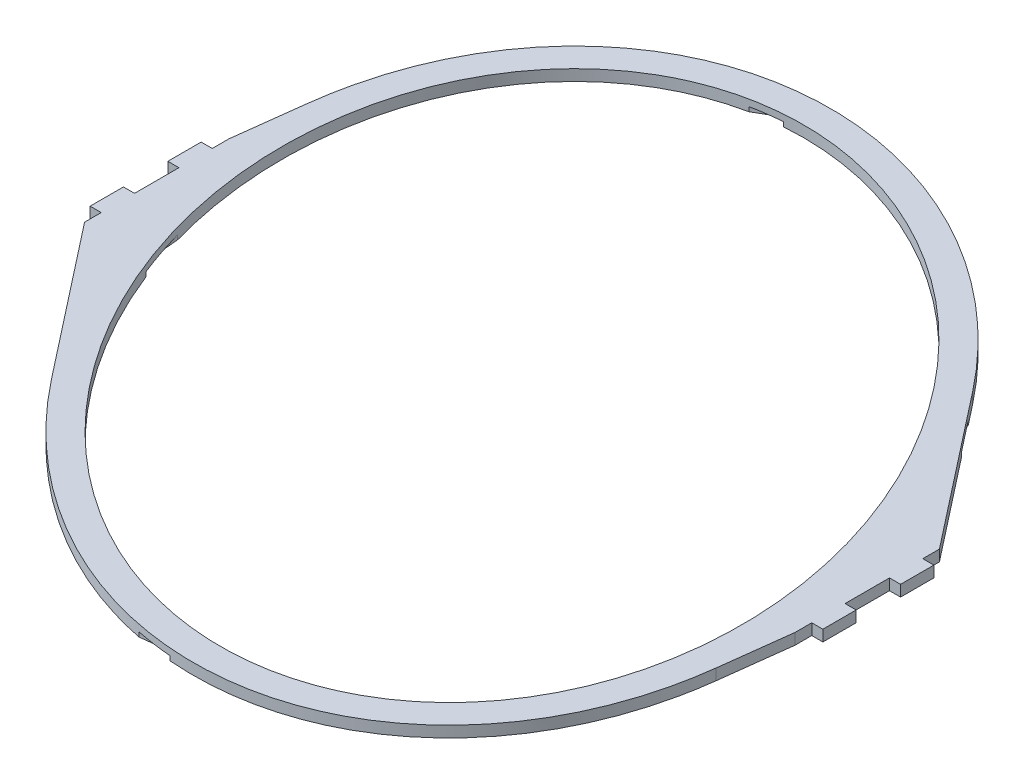
SolidWorks part; units mm, degrees
ref_plane "Front Plane" through (0, 0, 0) normal (0, 0, 1) x (1, 0, 0)
ref_plane "Top Plane" through (0, 0, 0) normal (0, 1, 0) x (1, 0, 0)
ref_plane "Right Plane" through (0, 0, 0) normal (1, 0, 0) x (0, 0, -1)
sketch "Sketch1" plane through (0, 0, 0) normal (0, 1, 0) x (1, 0, 0)
  line L0 (0, 520.2694) -> (0, -520.3963) construction
  line L1 (-478.2136, 0) -> (435.079, 0) construction
  line L2 (-270, 0) -> (-270, 60) construction
  line L3 (-270, 60) -> (-290, 60) construction
  line L4 (-290, 60) -> (-290, -60) construction
  line L5 (-320, 50) -> (-320, 65)
  line L6 (-330, -20) -> (-330, -50)
  line L7 (-320, -50) -> (-320, -65)
  line L8 (-330, -50) -> (-320, -50)
  line L9 (290, 60) -> (290, -60) construction
  line L10 (-320, -20) -> (-330, -20)
  line L11 (-320, 0) -> (-320, -20)
  line L12 (-320, 0) -> (-320, 20)
  line L13 (-320, 20) -> (-330, 20)
  line L14 (-330, 20) -> (-330, 50)
  line L15 (-330, 50) -> (-320, 50)
  line L16 (-320, 65) -> (-312.1702, 128.3352)
  line L17 (-320, -65) -> (-212.2821, -202.5885)
  line L19 (-290, 60) -> (-290, -60) construction
  line L29 (-177.5, 307.439) -> (177.5, -307.439) construction
  line L30 (320, 0) -> (320, 20)
  line L31 (320, 20) -> (330, 20)
  line L32 (330, 20) -> (330, 50)
  line L33 (330, 50) -> (320, 50)
  line L34 (320, 50) -> (320, 65)
  line L35 (320, 0) -> (320, -20)
  line L36 (320, -20) -> (330, -20)
  line L37 (330, -20) -> (330, -50)
  line L38 (330, -50) -> (320, -50)
  line L39 (320, -50) -> (320, -65)
  line L40 (320, -65) -> (312.1702, -128.3352)
  line L41 (320, 65) -> (212.2821, 202.5885)
  ellipse E0 centre (0, 0) end of major axis (-190, 329.0897) minor radius 290 (212.2821, 202.5885) -> (-312.1702, 128.3352) ccw
  ellipse E1 centre (0, 0) end of major axis (0, 380) minor radius 290 construction
  ellipse E3 centre (0, 0) end of major axis (-177.5, 307.439) minor radius 265
  ellipse E7 centre (0, 0) end of major axis (-190, 329.0897) minor radius 290 (-212.2821, -202.5885) -> (312.1702, -128.3352) ccw
  point P27 (290, 0)
  point P32 (-290, 0)
  point P42 (290, 0)
  dimension "D2" = 10
  dimension "D3" = 580
  dimension "D4" = 760
  dimension "D5" = 20
  dimension "D6" = 10
  dimension "D7" = 60
  dimension "D8" = 10
  dimension "D9" = 320
  dimension "D10" = 30
  dimension "D11" = 710
  dimension "D12" = 530
  dimension "D13" = 760
  dimension "D14" = 580
  dimension "D15" = 30
  dimension "D16" = 30
  dimension "D17" = 20
  dimension "D18" = 20
  dimension "D19" = 15
  dimension "D20" = 15
extrude "Boss-Extrude1" add sketch "Sketch1" along normal blind 10
sketch "Sketch2" plane through (0, 0, 0) normal (0, -1, 0) x (1, 0, 0)
  line L0 (0, -520.2694) -> (0, 520.3963) construction
  ellipse E0 centre (0, 0) end of major axis (0, 355) minor radius 265
  ellipse E2 centre (0, 0) end of major axis (0, 365) minor radius 275
  dimension "D1" = 10
  dimension "D2" = 10
extrude "Cut-Extrude1" cut sketch "Sketch2" against normal blind 4
sketch "Sketch4" plane through (-290, 0, 0) normal (-1, 0, 0) x (0, 0, 1)
  line L0 (-2.5, 0) -> (2.5, 0)
  arc A0 (2.5, 0) -> (-2.5, 0) centre (0, 0) ccw
  dimension "D1" = 5
extrude "Cut-Extrude4" cut sketch "Sketch4" against normal blind 10 from surface rebuild error yes
sketch "Sketch5" plane through (290, 0, 0) normal (1, 0, 0) x (0, 0, -1)
  line L1 (-2.5, 0) -> (2.5, 0)
  line L2 (-20, 0) -> (20, 0) construction
  arc A0 (2.5, 0) -> (-2.5, 0) centre (0, 0) ccw
  dimension "D1" = 5
extrude "Cut-Extrude5" cut sketch "Sketch5" against normal blind 10
